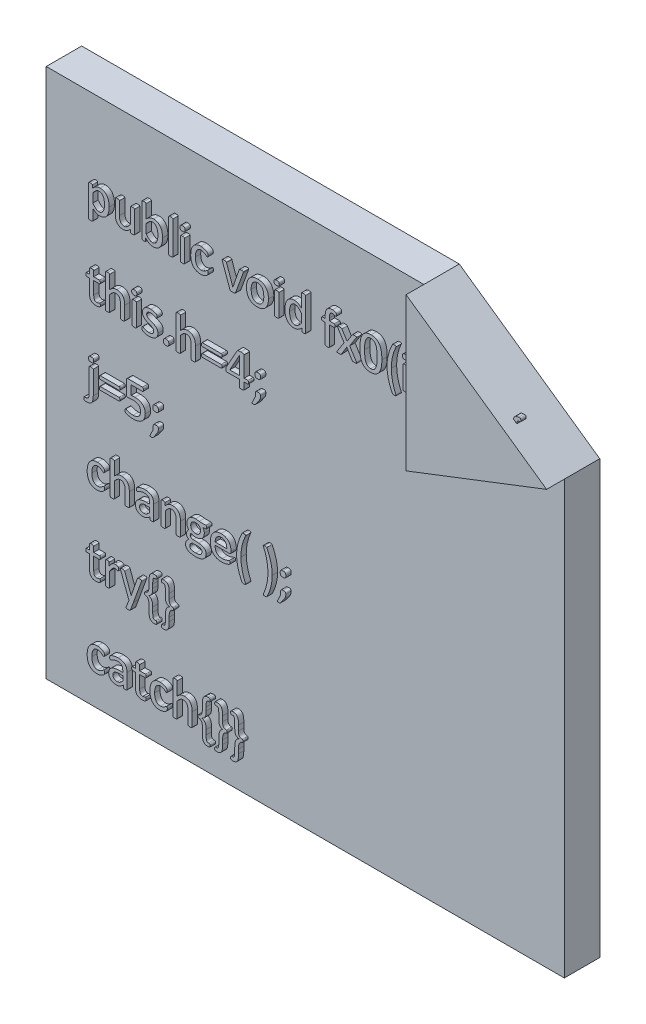
SolidWorks part; units mm, degrees
ref_plane "Plano frontal" through (0, 0, 0) normal (0, 0, 1) x (1, 0, 0)
ref_plane "Plano superior" through (0, 0, 0) normal (0, 1, 0) x (1, 0, 0)
ref_plane "Plano direito" through (0, 0, 0) normal (1, 0, 0) x (0, 0, -1)
sketch "Esboço1" plane through (0, 0, 0) normal (0, 0, 1) x (1, 0, 0)
  line L0 (-20.2651, 13.207) -> (-20.2651, -16.7206)
  line L1 (-20.2651, -16.7206) -> (8.9688, -16.7206)
  line L2 (8.9688, -16.7206) -> (8.9688, 7.6575)
  line L3 (8.9688, 7.6575) -> (1.041, 13.207)
  line L4 (1.041, 13.207) -> (-20.2651, 13.207)
extrude "Ressalto-extrusão2" add sketch "Esboço1" along normal blind 2
sketch "Esboço3" plane through (0, 0, 2) normal (0, 0, 1) x (1, 0, 0)
  line L0 (1.041, 13.207) -> (1.041, 4.597)
  line L1 (1.041, 4.597) -> (8.9688, 7.6575)
  line L2 (8.9688, 7.6575) -> (1.041, 13.207)
extrude "Ressalto-extrusão3" add sketch "Esboço3" along normal blind 1
sketch "Esboço4" plane through (0, 0, 2) normal (0, 0, 1) x (1, 0, 0)
  text T0 "public void fx0(int e){\r\nthis.h=4;\r\nj=5;\r\nchange( );\r\ntry{}\r\ncatch{}}" font "Calibri" height in points 7
extrude "Ressalto-extrusão4" add sketch "Esboço4" along normal blind 0.3
